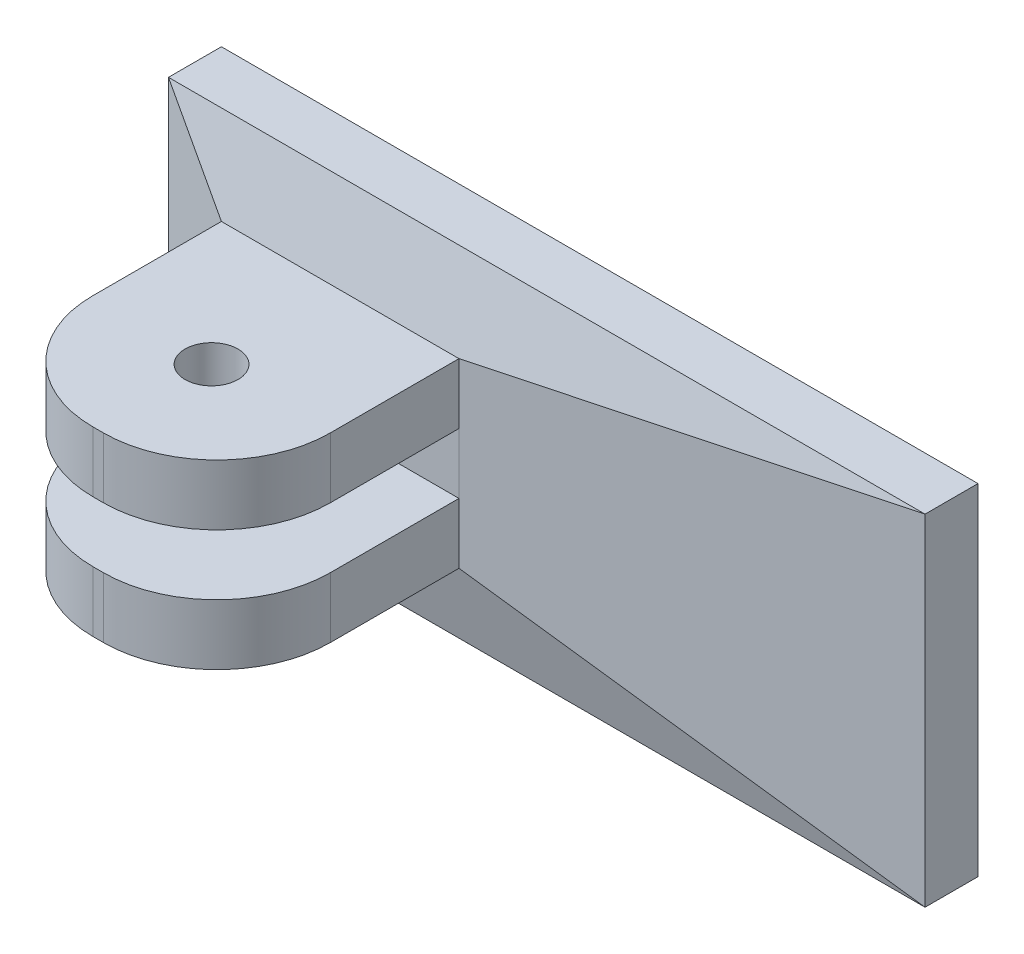
SolidWorks part; units mm, degrees
ref_plane "Front Plane" through (0, 0, 0) normal (0, 0, 1) x (1, 0, 0)
ref_plane "Top Plane" through (0, 0, 0) normal (0, 1, 0) x (1, 0, 0)
ref_plane "Right Plane" through (0, 0, 0) normal (1, 0, 0) x (0, 0, -1)
sketch "Sketch1" plane through (0, 0, 0) normal (0, 0, 1) x (1, 0, 0)
  line L0 (-36.8379, 0) -> (35.7924, 0) construction
  line L1 (-9.658, 0) -> (9.6311, 0) construction
  line L2 (0, 28.0357) -> (0, -21.5283) construction
  line L16 (-23.95, 14.8522) -> (76.05, 14.8522)
  line L17 (-23.95, 14.8522) -> (-23.95, -30.1478)
  line L18 (-23.95, -30.1478) -> (76.05, -30.1478)
  line L19 (76.05, 14.8522) -> (76.05, -30.1478)
  dimension "D1" = 100
  dimension "D2" = 45
extrude "Boss-Extrude1" add sketch "Sketch1" along normal blind 10
sketch "Sketch3" plane through (0, 0, 10) normal (0, 0, 1) x (1, 0, 0)
  line L0 (76.05, 14.8522) -> (-23.95, 14.8522) construction
  line L1 (-13.95, 4.8522) -> (17.45, 4.8522)
  line L2 (-13.95, 4.8522) -> (-13.95, -3.1478)
  line L3 (-13.95, -3.1478) -> (17.45, -3.1478)
  line L4 (17.45, 4.8522) -> (17.45, -3.1478)
  line L5 (-23.95, 14.8522) -> (-23.95, -30.1478) construction
  dimension "D1" = 31.4
  dimension "D2" = 8
  dimension "D3" = 10
  dimension "D4" = 10
extrude "Boss-Extrude2" add sketch "Sketch3" along normal blind 5
sketch "Sketch4" plane through (0, -3.1478, 0) normal (0, -1, 0) x (1, 0, 0)
  line L0 (-13.95, 15) -> (-13.95, 27)
  line L1 (1.05, 42) -> (2.45, 42)
  line L2 (17.45, 27) -> (17.45, 15)
  line L3 (-13.95, 15) -> (17.45, 15)
  arc A0 (-13.95, 27) -> (1.05, 42) centre (1.05, 27) cw
  arc A1 (2.45, 42) -> (17.45, 27) centre (2.45, 27) cw
  circle A2 centre (1.7449, 27) radius 3.5
  point P11 (17.45, 42)
  dimension "D2" = 15
  dimension "D3" = 15
  dimension "D1" = 27
extrude "Boss-Extrude3" add sketch "Sketch4" against normal blind 8
ref_plane "Plane1" through (0, -7.1478, 0) normal (0, -1, 0) x (-1, 0, 0)
mirror "Mirror1" about plane through (0, -7.1478, 0) normal (0, -1, 0) of "Boss-Extrude3", "Boss-Extrude2"
sketch "Sketch5" plane through (0, -30.1478, 0) normal (0, -1, 0) x (1, 0, 0)
  line L0 (-13.95, 10) -> (-23.95, 7)
  line L1 (-23.95, 10) -> (-23.95, 0) construction
  line L2 (-23.95, 7) -> (-23.95, 10)
  line L3 (-23.95, 10) -> (-13.95, 10)
  line L4 (17.45, 10) -> (76.05, 7)
  line L5 (76.05, 10) -> (76.05, 0) construction
  line L6 (76.05, 7) -> (76.05, 10)
  line L7 (76.05, 10) -> (17.45, 10)
  dimension "D1" = 3
  dimension "D2" = 3
extrude "Cut-Extrude1" cut sketch "Sketch5" against normal blind 45
sketch "Sketch6" plane through (-23.95, 0, 0) normal (-1, 0, 0) x (0, 0, 1)
  line L0 (7, 14.8522) -> (10, 4.8522)
  line L1 (10, 4.8522) -> (10, 14.8522)
  line L2 (10, 14.8522) -> (7, 14.8522)
  line L3 (10, -19.1478) -> (7, -30.1478)
  line L4 (7, -30.1478) -> (10, -30.1478)
  line L5 (10, -30.1478) -> (10, -19.1478)
extrude "Cut-Extrude2" cut sketch "Sketch6" against normal blind 100
